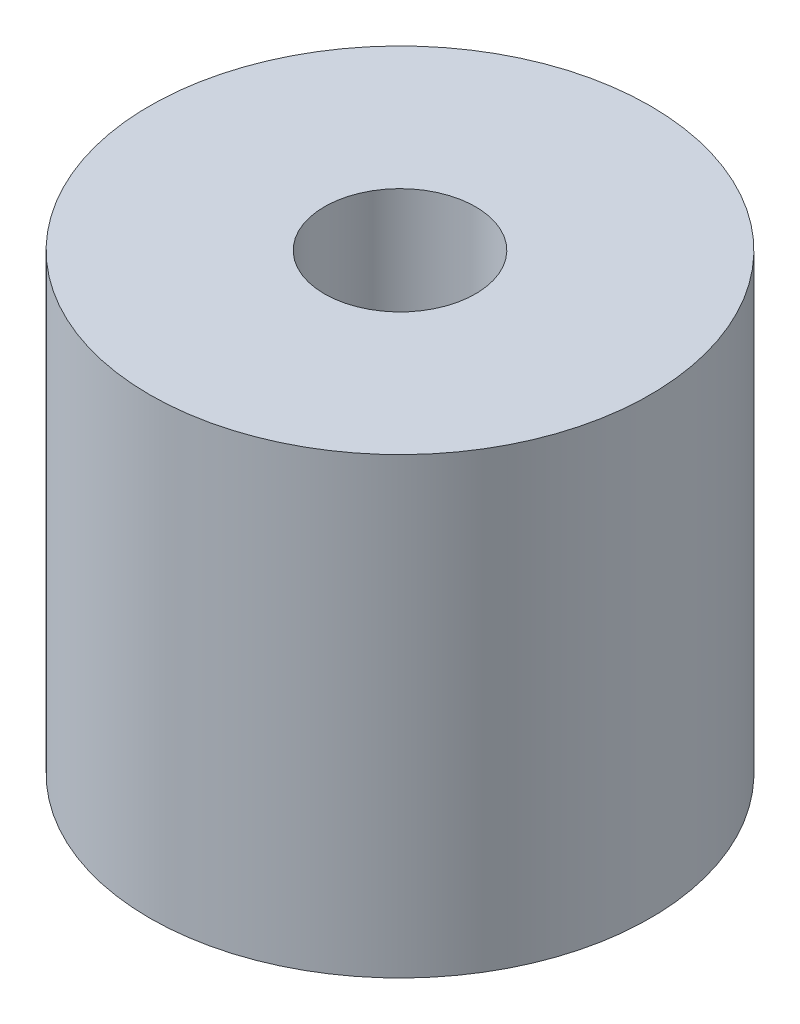
SolidWorks part; units mm, degrees
ref_plane "前视基准面" through (0, 0, 0) normal (0, 0, 1) x (1, 0, 0)
ref_plane "上视基准面" through (0, 0, 0) normal (0, 1, 0) x (1, 0, 0)
ref_plane "右视基准面" through (0, 0, 0) normal (1, 0, 0) x (0, 0, -1)
other "Configuration Table"
sketch "草图1" plane through (0, 0, 0) normal (0, 1, 0) x (1, 0, 0)
  circle A0 centre (0, 0) radius 2.65
  dimension "D2" = 5.3
extrude "凸台-拉伸1" add sketch "草图1" along normal blind 4.8 contours A0
sketch "草图2" plane through (0, 4.8, 0) normal (0, 1, 0) x (1, 0, 0)
  circle A0 centre (0, 0) radius 1.6
  circle A1 centre (0, 0) radius 0.8
  dimension "D1" = 3.2
  dimension "D2" = 1.6
extrude "切除-拉伸1" cut sketch "草图2" against normal through all contours A1
